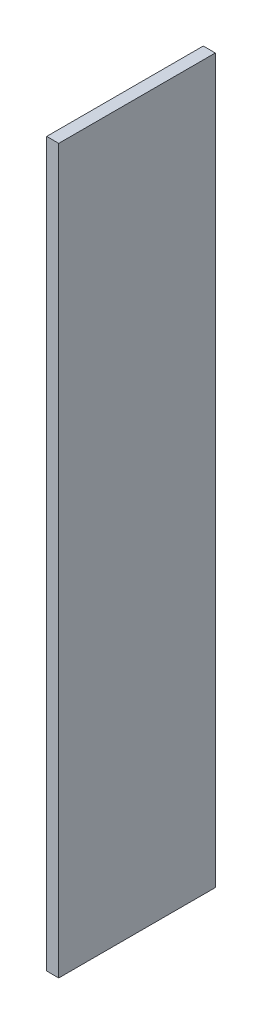
SolidWorks part; units mm, degrees
ref_plane "Plan de face" through (0, 0, 0) normal (0, 0, 1) x (1, 0, 0)
ref_plane "Plan de dessus" through (0, 0, 0) normal (0, 1, 0) x (1, 0, 0)
ref_plane "Plan de droite" through (0, 0, 0) normal (1, 0, 0) x (0, 0, -1)
sketch "Esquisse1" plane through (0, 0, 0) normal (0, 0, 1) x (1, 0, 0)
  line L0 (-109.309, 0) -> (-222.1354, 0) construction
  line L1 (-155.642, 600) -> (-165.642, 600)
  line L2 (-155.642, 600) -> (-155.642, 0)
  line L3 (-155.642, 0) -> (-165.642, 0)
  line L4 (-165.642, 600) -> (-165.642, 0)
  dimension "D1" = 10
extrude "Boss.-Extru.1" add sketch "Esquisse1" along normal up to surface (129.974 mm away)
